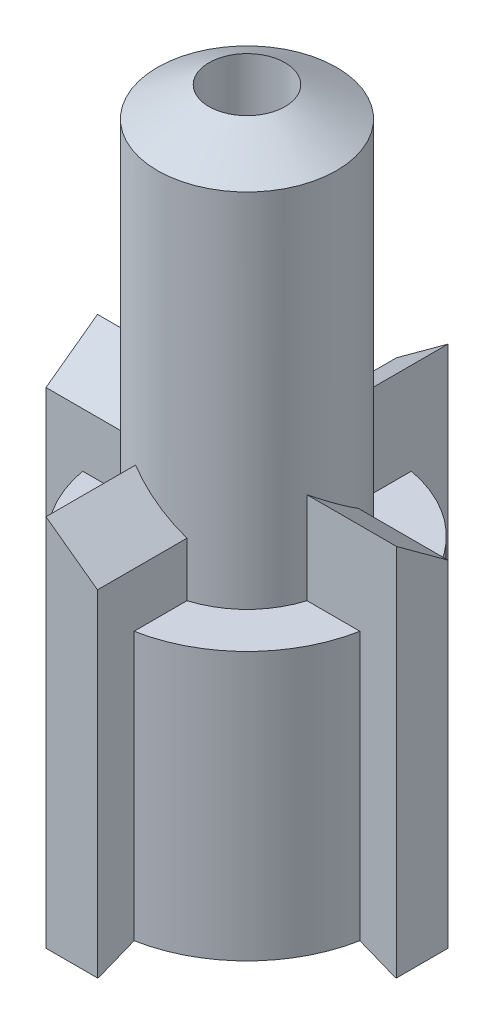
SolidWorks part; units mm, degrees
material "PP Copolymer"
ref_plane "Front Plane" through (0, 0, 0) normal (0, 0, 1) x (1, 0, 0)
ref_plane "Top Plane" through (0, 0, 0) normal (0, 1, 0) x (1, 0, 0)
ref_plane "Right Plane" through (0, 0, 0) normal (1, 0, 0) x (0, 0, -1)
ref_axis "X-axis" through (-88.99, 0, 0) along (1, 0, 0)
ref_axis "Y-axis" through (0, 55, 0) along (0, -1, 0)
ref_axis "Z-axis" through (0, 0, -88.99) along (0, 0, 1)
sketch "Sketch1" plane through (0, 0, 0) normal (0, 0, 1) x (1, 0, 0)
  line L0 (0, 0) -> (0, 14.95) construction
  line L1 (-3.15, 0) -> (-1.85, 0.7506)
  line L2 (-1.85, 0.7506) -> (-1.85, 5.3479)
  line L3 (-1.85, 5.3479) -> (-0.85, 5.3479)
  line L4 (-0.85, 5.3479) -> (-0.85, 14.95)
  line L5 (-0.85, 14.95) -> (-2, 14.286)
  line L6 (-2, 14.286) -> (-2, 6.21)
  line L7 (-2, 6.21) -> (-3.15, 6.21)
  line L8 (-3.15, 6.21) -> (-3.15, 0)
  dimension "D1" = 14.95
  dimension "D2" = 1.7
  dimension "D3" = 1.3
  dimension "D4" = 6.21
  dimension "D5" = 60
  dimension "D6" = 9.6021
  dimension "D7" = 4
  dimension "D8" = 6.3
revolve "Revolve1" add sketch "Sketch1" angle 360 about L0
sketch "Sketch3" plane through (0, 6.21, 0) normal (0, 1, 0) x (1, 0, 0)
  line L1 (-0.575, -3.9156) -> (0.575, -3.9156)
  line L2 (-0.575, -3.9156) -> (-0.575, -1.9156)
  line L4 (0.575, -3.9156) -> (0.575, -1.9156)
  line L5 (-0.575, -3.9156) -> (0.575, -1.9156) construction
  line L6 (-0.575, -1.9156) -> (0.575, -3.9156) construction
  circle A0 centre (0, 0) radius 2 construction
  arc A1 (-0.575, -1.9156) -> (0.575, -1.9156) centre (0, 0) ccw
  point P0 (0, -2.9156)
  dimension "D1" = 1.15
  dimension "D2" = 2
  dimension "D3" = 3.9156
extrude "Boss-Extrude1" add sketch "Sketch3" against normal blind 6.3 and the other way blind 2.05
sketch "Sketch4" plane through (0, 0, 3.9156) normal (0, 0, 1) x (1, 0, 0)
  line L0 (0.575, 7.4203) -> (-0.575, 8.26)
  line L1 (0.575, 8.26) -> (0.575, -0.09) construction
  line L2 (-0.575, 8.26) -> (0.575, 8.26) construction
  line L3 (0.575, 8.26) -> (0.575, 7.4203)
  line L4 (-0.575, 8.26) -> (0.575, 8.26)
extrude "Cut-Extrude1" cut sketch "Sketch4" against normal up to surface (2.1572 mm away) up to face at (0, 5.3479, -1.85)
pattern_circular "CirPattern3" count 4 over 360 about axis through (0, 14.286, 0) along (0, -1, 0) of "Boss-Extrude1", "Cut-Extrude1"
sketch "Sketch9" plane through (0, 0, 0) normal (0, 0, 1) x (1, 0, 0)
  line L0 (-3.9156, -0.09) -> (-1.85, 0.7506)
  line L1 (-1.85, 0.7506) -> (-1.85, -0.09)
  line L2 (-1.85, -0.09) -> (-3.9156, -0.09)
revolve "Cut-Revolve2" cut sketch "Sketch9" angle 360 about axis through (0, 0, 0) along (0, -1, 0)
sketch "Sketch10" plane through (0, 0, 0) normal (0, 0, 1) x (1, 0, 0)
  line L0 (-2, 8.26) -> (-2, 6.21)
  line L1 (-3.0971, 6.21) -> (-1.9156, 6.21) construction
  line L2 (-2, 6.21) -> (-1.9156, 6.21)
  line L3 (-1.9156, 6.21) -> (-1.9156, 8.26)
  line L4 (-1.9156, 8.26) -> (-2, 8.26)
revolve "Revolve2" add sketch "Sketch10" angle 360 about axis through (0, 0, 0) along (0, -1, 0)
